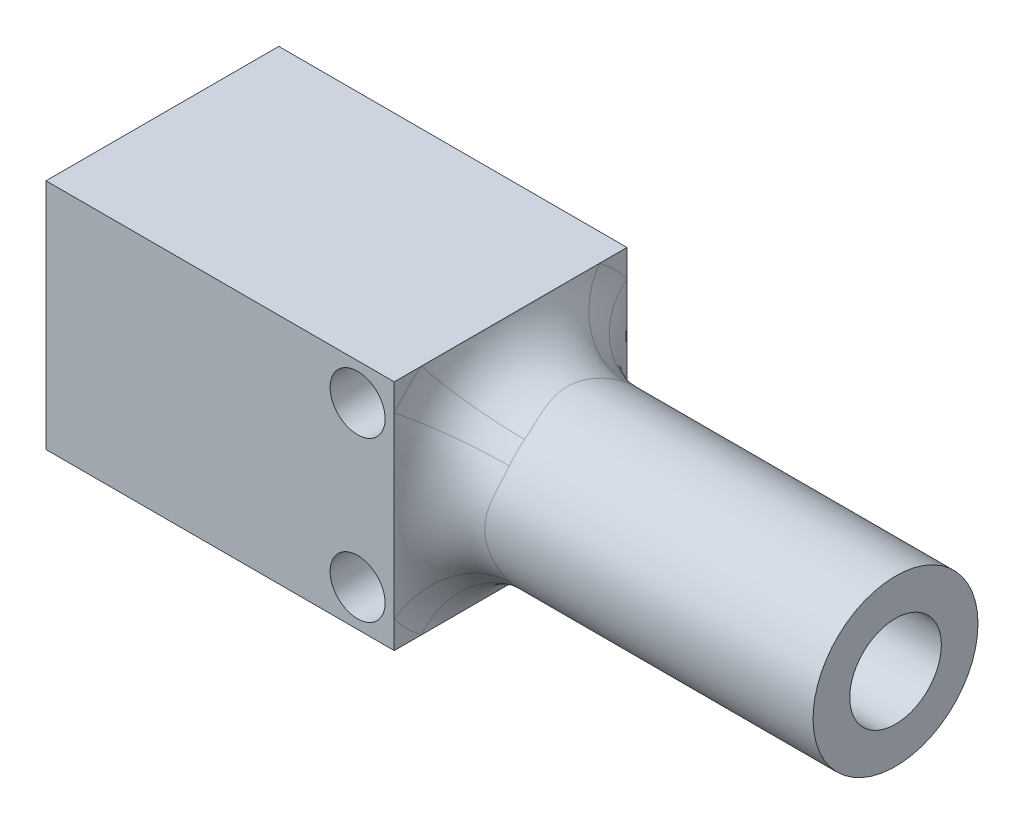
SolidWorks part; units mm, degrees
ref_plane "Ebene vorne" through (0, 0, 0) normal (1, 0, 0) x (0, 1, 0)
ref_plane "Ebene oben" through (0, 0, 0) normal (0, 0, 1) x (0, 1, 0)
ref_plane "Ebene rechts" through (0, 0, 0) normal (0, 1, 0) x (-1, 0, 0)
sketch "Skizze5" plane through (0, 0, 0) normal (1, 0, 0) x (0, 1, 0)
  line L1 (-12.7, -12.7) -> (12.7, -12.7)
  line L2 (-12.7, -12.7) -> (-12.7, 12.7)
  line L3 (-12.7, 12.7) -> (12.7, 12.7)
  line L4 (12.7, -12.7) -> (12.7, 12.7)
  line L5 (-12.7, -12.7) -> (12.7, 12.7) construction
  line L6 (-12.7, 12.7) -> (12.7, -12.7) construction
  point P0 (0, 0)
  dimension "D1" = 25.4
  dimension "D2" = 25.4
extrude "Motorarm" add sketch "Skizze5" along normal blind 60 and the other way blind 20
sketch "Skizze6" plane through (60, 0, 0) normal (1, 0, 0) x (0, 1, 0)
  circle A0 centre (0, 0) radius 5
  dimension "D1" = 10
extrude "Welle" cut sketch "Skizze6" against normal blind 100
sketch "Skizze7" plane through (-20, 0, 0) normal (-1, 0, 0) x (0, -1, 0)
  line L5 (-8.5, -8.5) -> (8.5, 8.5) construction
  line L6 (-8.5, 8.5) -> (8.5, -8.5) construction
  circle A0 centre (-8.5, 8.5) radius 2
  circle A1 centre (8.5, 8.5) radius 2
  circle A2 centre (-8.5, -8.5) radius 2
  circle A3 centre (8.5, -8.5) radius 2
  point P0 (0, 0)
  dimension "D1" = 17
  dimension "D2" = 17
extrude "Löcher AS5600" cut sketch "Skizze7" against normal blind 7
sketch "Skizze9" plane through (0, 0, -12.7) normal (0, 0, -1) x (1, 0, 0)
  line L8 (0, 9.5) -> (-8.2272, 4.75) construction
  line L9 (-8.2272, 4.75) -> (-8.2272, -4.75) construction
  line L10 (-8.2272, -4.75) -> (0, -9.5) construction
  line L11 (0, -9.5) -> (8.2272, -4.75) construction
  line L12 (8.2272, -4.75) -> (8.2272, 4.75) construction
  line L13 (8.2272, 4.75) -> (0, 9.5) construction
  circle A4 centre (0, 0) radius 8.2272 construction
  circle A5 centre (0, 9.5) radius 2
  circle A6 centre (8.2272, 4.75) radius 2
  circle A7 centre (8.2272, -4.75) radius 2
  circle A8 centre (0, -9.5) radius 2
  circle A9 centre (-8.2272, -4.75) radius 2
  circle A10 centre (-8.2272, 4.75) radius 2
  circle A11 centre (0, 0) radius 12.7 construction
extrude "Löcher Motoraufnahme" cut sketch "Skizze9" against normal blind 7
sketch "Skizze10" plane through (0, 0, 0) normal (1, 0, 0) x (0, 1, 0)
  circle A0 centre (0, 0) radius 6.5
  dimension "D1" = 13
extrude "Kugellager 1" cut sketch "Skizze10" along normal blind 5 from offset 12
sketch "Skizze11" plane through (0, 0, 0) normal (1, 0, 0) x (0, 1, 0)
  circle A0 centre (0, 0) radius 6.5
  dimension "D1" = 13
extrude "Kugellager 2" cut sketch "Skizze11" along normal blind 5 from offset 40
sketch "Skizze12" plane through (0, 0, 0) normal (1, 0, 0) x (0, 1, 0)
  circle A1 centre (0, 0) radius 9
  dimension "D1" = 18
extrude "Materialreduzierung" cut sketch "Skizze12" along normal blind 42 from offset 18 flip side to cut
fillet "Übergang" radius 7 1 edges at (18, 0, -9)
sketch "Skizze14" plane through (0, 0, -12.7) normal (0, 0, -1) x (1, 0, 0)
  line L15 (18, 12.7) -> (14, 12.7) construction
  line L16 (18, 12.7) -> (18, 8.7) construction
  line L17 (18, 8.7) -> (14, 8.7) construction
  line L18 (14, 12.7) -> (14, 8.7) construction
  line L19 (17.3, 8.7) -> (15.65, 11.5579)
  line L20 (15.65, 11.5579) -> (12.35, 11.5579)
  line L21 (12.35, 11.5579) -> (10.7, 8.7)
  line L22 (10.7, 8.7) -> (12.35, 5.8421)
  line L23 (12.35, 5.8421) -> (15.65, 5.8421)
  line L24 (15.65, 5.8421) -> (17.3, 8.7)
  line L25 (18, -12.7) -> (14, -12.7) construction
  line L26 (18, -12.7) -> (18, -8.7) construction
  line L27 (18, -8.7) -> (14, -8.7) construction
  line L28 (14, -12.7) -> (14, -8.7) construction
  line L29 (17.3, -8.7) -> (15.65, -5.8421)
  line L30 (15.65, -5.8421) -> (12.35, -5.8421)
  line L31 (12.35, -5.8421) -> (10.7, -8.7)
  line L32 (10.7, -8.7) -> (12.35, -11.5579)
  line L33 (12.35, -11.5579) -> (15.65, -11.5579)
  line L34 (15.65, -11.5579) -> (17.3, -8.7)
  circle A0 centre (14, 8.7) radius 3.3 construction
  circle A1 centre (14, 8.7) radius 2.8579 construction
  circle A2 centre (14, -8.7) radius 3.3 construction
  circle A3 centre (14, -8.7) radius 2.8579 construction
  dimension "D3" = 4
  dimension "D1" = 4
  dimension "D2" = 4
  dimension "D4" = 4
extrude "Platz für Muttern" cut sketch "Skizze14" against normal blind 3
sketch "Skizze17" plane through (0, 0, -12.7) normal (0, 0, -1) x (1, 0, 0)
  circle A0 centre (14, -8.7) radius 3.3 construction
  circle A1 centre (14, -8.7) radius 1.6
  circle A2 centre (14, 8.7) radius 3.3 construction
  circle A3 centre (14, 8.7) radius 1.6
  dimension "D1" = 3.2
extrude "Platz für Stange" cut sketch "Skizze17" against normal blind 25.4
sketch "Skizze18" plane through (0, 0, 12.7) normal (0, 0, 1) x (1, 0, 0)
  circle A0 centre (14, 8.7) radius 3
  circle A1 centre (14, -8.7) radius 3
  dimension "D1" = 6
extrude "Platz für Schraubenkopf" cut sketch "Skizze18" against normal blind 6
sketch "Skizze21" plane through (0, 0, 0) normal (0, 0, 1) x (0, 1, 0)
  line L0 (-9, -60) -> (9, -60) construction
  line L1 (-12.7, 20) -> (-8.7, 20) construction
  line L2 (-12.7, 20) -> (-12.7, 10) construction
  line L3 (-12.7, 10) -> (-8.7, 10) construction
  line L4 (-8.7, 20) -> (-8.7, 10) construction
  line L5 (12.7, 20) -> (8.7, 20) construction
  line L6 (12.7, 20) -> (12.7, 10) construction
  line L7 (12.7, 10) -> (8.7, 10) construction
  line L8 (8.7, 20) -> (8.7, 10) construction
  line L9 (9, -60) -> (7, -60) construction
  line L10 (9, -60) -> (9, -54) construction
  line L11 (9, -54) -> (7, -54) construction
  line L12 (7, -60) -> (7, -54) construction
  line L14 (-9, -60) -> (-7, -60) construction
  line L15 (-9, -60) -> (-9, -54) construction
  line L16 (-9, -54) -> (-7, -54) construction
  line L17 (-7, -60) -> (-7, -54) construction
  circle A0 centre (-8.7, 10) radius 1
  circle A1 centre (8.7, 10) radius 1
  circle A2 centre (-7, -54) radius 1
  circle A3 centre (7, -54) radius 1
  dimension "D1" = 6
  dimension "D2" = 2
  dimension "D3" = 6
  dimension "D4" = 2
  dimension "D5" = 10
  dimension "D6" = 4
  dimension "D7" = 4
  dimension "D8" = 10
extrude "Platz für Fixierung" cut sketch "Skizze21" against normal blind 2.5 and the other way blind 2.5
